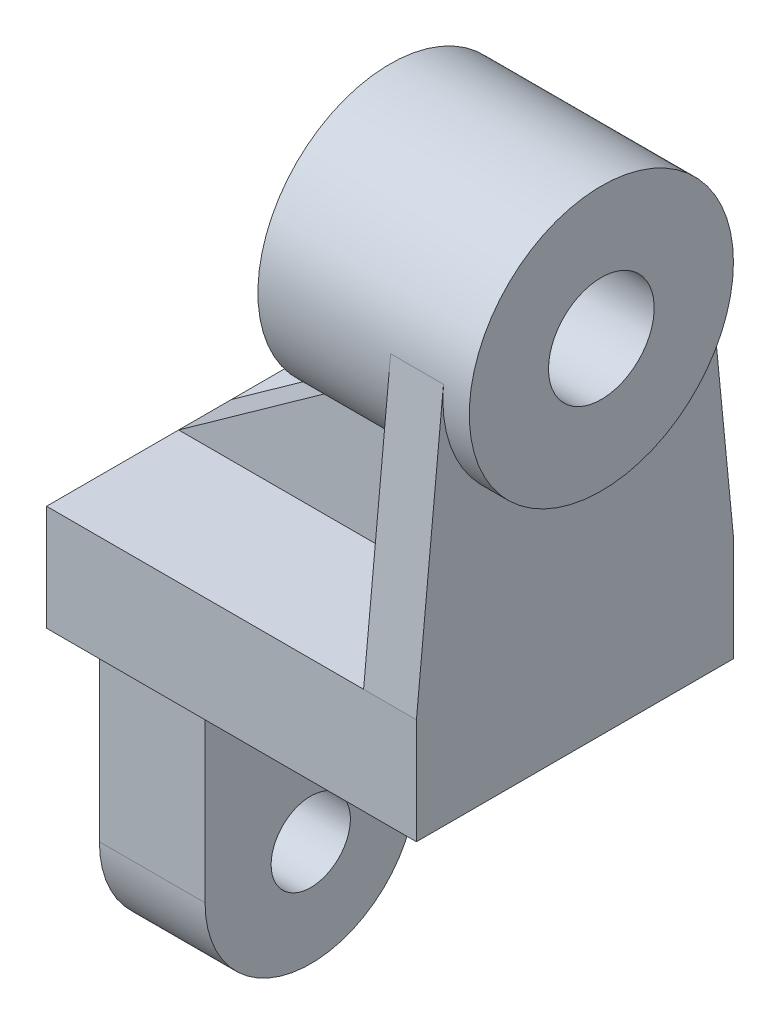
SolidWorks part; units mm, degrees
ref_plane "Ön Düzlem" through (0, 0, 0) normal (0, 0, 1) x (1, 0, 0)
ref_plane "Üst Düzlem" through (0, 0, 0) normal (0, 1, 0) x (1, 0, 0)
ref_plane "Sağ Düzlem" through (0, 0, 0) normal (1, 0, 0) x (0, 0, -1)
sketch "Sketch1" plane through (0, 0, 0) normal (1, 0, 0) x (0, 0, -1)
  line L1 (-30, -10) -> (30, -10)
  line L2 (-30, -10) -> (-30, 10)
  line L3 (-30, 10) -> (30, 10)
  line L4 (30, -10) -> (30, 10)
  line L5 (-30, -10) -> (30, 10) construction
  line L6 (-30, 10) -> (30, -10) construction
  point P0 (0, 0)
  dimension "D1" = 20
  dimension "D2" = 60
extrude "Boss-Extrude1" add sketch "Sketch1" against normal blind 70
sketch "Sketch3" plane through (0, 0, 0) normal (1, 0, 0) x (0, 0, -1)
  line L0 (0, 0) -> (0, 60) construction
  line L1 (-30, 10) -> (-24.8817, 62.429)
  line L2 (30, 10) -> (24.8817, 62.429)
  line L3 (-30, 10) -> (30, 10)
  arc A0 (24.8817, 62.429) -> (-24.8817, 62.429) centre (0, 60) ccw
  dimension "D2" = 50
  dimension "D1" = 60
extrude "Boss-Extrude2" add sketch "Sketch3" against normal blind 10
sketch "Sketch4" plane through (0, 0, 0) normal (1, 0, 0) x (0, 0, -1)
  circle A0 centre (0, 60) radius 25
  dimension "D1" = 50
extrude "Boss-Extrude3" add sketch "Sketch4" along normal blind 5 and the other way blind 35
sketch "Sketch5" plane through (-35, 0, 0) normal (-1, 0, 0) x (0, 0, 1)
  circle A0 centre (0, 60) radius 15
  dimension "D1" = 30
extrude "Cut-Extrude1" cut sketch "Sketch5" against normal blind 6
sketch "Sketch6" plane through (-35, 0, 0) normal (-1, 0, 0) x (0, 0, 1)
  circle A0 centre (0, 60) radius 10
  dimension "D1" = 20
extrude "Cut-Extrude2" cut sketch "Sketch6" against normal through all
ref_plane "Plane2" through (0, 0, 0) normal (0, 0, 1) x (1, 0, 0)
sketch "Sketch9" plane through (0, 0, 0) normal (0, 0, 1) x (1, 0, 0)
  line L0 (-35, 35) -> (-70, 10)
rib "Rib1" sketch "Sketch9" sketch "Sketch9" thickness 10 extrusion direction parallel to sketch draft on no parameters "D1"=10
sketch "Sketch14" plane through (-70, 0, 0) normal (-1, 0, 0) x (0, 0, 1)
  line L0 (30, -10) -> (-30, -10) construction
  line L1 (-20, -10) -> (20, -10)
  line L2 (-20, -10) -> (-20, -50)
  line L4 (20, -10) -> (20, -50)
  arc A0 (-20, -50) -> (20, -50) centre (0, -50) ccw
  circle A1 centre (0, -50) radius 7.5
  dimension "D1" = 15
  dimension "D2" = 10
  dimension "D3" = 40
extrude "Boss-Extrude4" add sketch "Sketch14" against normal blind 20
fillet "Fillet3" radius 10 2 edges at (-60, -10, -20) (-60, -10, 20)
